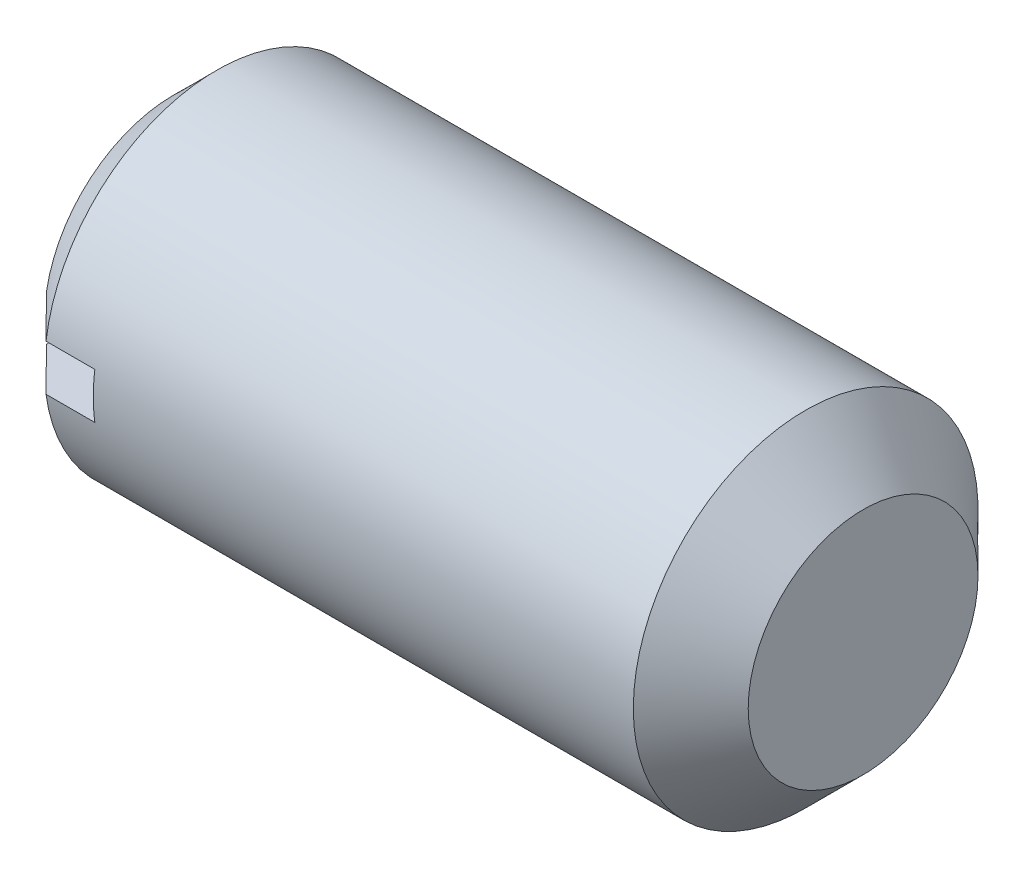
SolidWorks part; units mm, degrees
ref_plane "Front" through (0, 0, 0) normal (0, 0, 1) x (1, 0, 0)
ref_plane "Top" through (0, 0, 0) normal (0, 1, 0) x (1, 0, 0)
ref_plane "Right" through (0, 0, 0) normal (1, 0, 0) x (0, 0, -1)
sketch "Sketch1" plane through (0, 0, 0) normal (0, 0, 1) x (1, 0, 0)
  line L0 (0, 0) -> (6, 0)
  line L1 (6, 0) -> (6, 1)
  line L2 (6, 1) -> (5.5, 1.5)
  line L3 (5.5, 1.5) -> (0.375, 1.5)
  line L4 (0.375, 1.5) -> (0, 1.125)
  line L5 (0, 1.125) -> (0, 0)
  line L6 (-10.745, 0) -> (0.8952, 0) construction
  dimension "D2" = 45
  dimension "D1" = 45
revolve "Base" add sketch "Sketch1" angle 360 about L6
cosmetic thread "ThreadCosmetic1" [suppressed] parameters "D2"=2.25
sketch "Sketch2" plane through (0, 0, 0) normal (0, 0, 1) x (1, 0, 0)
  line L1 (0, 0.2) -> (0.8, 0.2)
  line L2 (0, 0.2) -> (0, -0.2)
  line L3 (0, -0.2) -> (0.8, -0.2)
  line L4 (0.8, 0.2) -> (0.8, -0.2)
  line L5 (0, 1.125) -> (0, -1.125) construction
  dimension "m" = 0.2
extrude "Notch" cut sketch "Sketch2" against normal through all and the other way through all
sketch "Sketch3" plane through (0, 0, 0) normal (0, 0, 1) x (1, 0, 0)
  line L0 (0.375, 1.1752) -> (0.5625, 1.5)
  line L1 (0.5625, 1.5) -> (0.5625, 1.875)
  line L2 (0.5625, 1.875) -> (0.1875, 1.875)
  line L3 (0.1875, 1.875) -> (0.1875, 1.5)
  line L4 (0.1875, 1.5) -> (0.375, 1.1752)
  line L5 (0, 0) -> (1.5288, 0) construction
  line L6 (0.375, 1.5) -> (0.375, 0.2) construction
  dimension "D1" = 3
  dimension "D2" = 0.375
revolve "Cut-Revolve10" [suppressed] cut sketch "Sketch3" angle 360 about L5
pattern_linear "LPattern10" [suppressed] count 13 spacing 0.45 along (1, 0, 0) of bodies 103
equation "\"df@Sketch1\" = \"D2@ThreadCosmetic1\""
equation "\"m@Sketch2\" = \"n@Sketch2\" / 2"
equation "\"D1@Sketch3\" = \"d@Sketch1\""
equation "\"D2@Sketch3\" =  ( \"d@Sketch1\" - \"D2@ThreadCosmetic1\" )  / 2"
equation "\"D3@LPattern10\" = \"D2@Sketch3\" * 1.2"
equation "\"D1@LPattern10\" =  ( \"l@Sketch1\" -  ( \"d@Sketch1\" - \"df@Sketch1\" )  / 2 )  / \"D3@LPattern10\""
